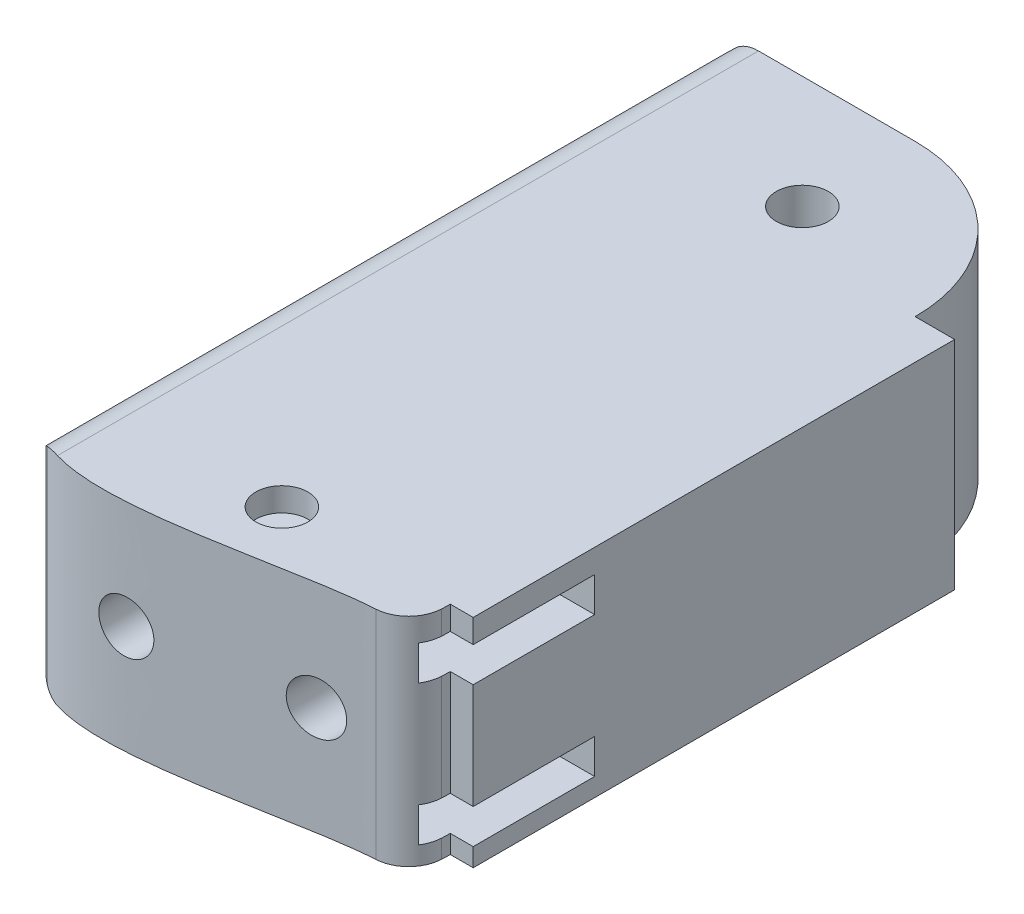
SolidWorks part; units mm, degrees
ref_plane "Front Plane" through (0, 0, 0) normal (0, 0, 1) x (1, 0, 0)
ref_plane "Top Plane" through (0, 0, 0) normal (0, 1, 0) x (1, 0, 0)
ref_plane "Right Plane" through (0, 0, 0) normal (1, 0, 0) x (0, 0, -1)
sketch "Sketch1" plane through (0, 0, 0) normal (0, 0, 1) x (1, 0, 0)
  line L0 (-24.2561, -24.0702) -> (-22.0061, -24.0702) construction
  line L1 (-24.2561, -17.8202) -> (-2.2017, -17.8202)
  line L2 (-24.2561, -17.8202) -> (-24.2561, -30.3202)
  line L3 (-24.2561, -30.3202) -> (-2.2017, -30.3202)
  line L4 (-2.2017, -17.8202) -> (-2.2017, -30.3202)
  line L5 (-2.2017, -24.0702) -> (-4.4517, -24.0702) construction
  line L6 (-22.0061, -24.0702) -> (-22.0061, -30.3202) construction
  line L7 (-4.4517, -24.0702) -> (-4.4517, -30.3202) construction
extrude "Boss-Extrude1" add sketch "Sketch1" along normal blind 43
sketch "Sketch2" plane through (0, -30.3202, 0) normal (0, -1, 0) x (1, 0, 0)
  line L0 (-3.524, 36.5) -> (-2.2017, 36.5)
  line L1 (-24.2561, 0) -> (-2.2017, 0) construction
  line L2 (-13.2289, 0) -> (-13.2289, 8.75) construction
  line L4 (-24.2561, 43) -> (-24.2561, 0) construction
  line L5 (-4.4789, 8.75) -> (-2.2017, 8.75)
  line L6 (-2.2017, 43) -> (-2.2017, 0) construction
  line L7 (-13.2289, 43) -> (-13.2289, 36.5) construction
  line L8 (-24.2561, 43) -> (-2.2017, 43) construction
  line L11 (-13.2289, 8.75) -> (-13.2289, 6.5) construction
  line L12 (-24.2561, 0) -> (-2.2017, 0) construction
  arc A1 (-13.2289, 0) -> (-4.4789, 8.75) centre (-13.2289, 8.75) ccw
  circle A4 centre (-13.2289, 6.5) radius 1.5
  arc A6 (-3.524, 36.5) -> (-3.8316, 38.9241) centre (-13.2289, 36.5) ccw
  circle A7 centre (-13.2289, 36.5) radius 1.5
  spline S0 degree 3 poles (-2.2017, 8.75) (5.3921, 3.8803) (-0.7771, -4.5233) (-17.1743, -10.6233) (-34.8214, -0.026) (-24.2561, 8.75) knots 0 0 0 0 0.283273 0.504245 1 1 1 1
  spline S1 degree 3 poles (-24.2561, 33.8451) (-30.4109, 43.5575) (-12.6056, 54.8557) (11.2773, 42.5746) (-2.2017, 36.5) knots 0 0 0 0 0.503105 1 1 1 1
  spline S2 degree 1 poles (-13.2289, 0) (-23.4906, 0) knots 0 0 1 1
  spline S3 degree 2 poles (-23.4906, 0) (-24.9665, 4.2378) (-24.2561, 8.75) knots 0 0 0 1 1 1
  spline S4 degree 3 poles (-3.8316, 38.9241) (-9.2507, 38.1251) (-28.5323, 46.1638) (-24.2561, 33.8451) knots 0 0 0 0 1 1 1 1
extrude "Cut-Extrude1" cut sketch "Sketch2" against normal blind 15 and the other way blind 10
fillet "Fillet3" radius 2 4 edges at (-24.2561, -17.8202, 21.0415) (-24.2561, -30.3202, 21.0415) (-24.2561, -24.0702, 3.0015) (-24.2561, -24.0702, 39.0815)
ref_plane "Plane1" through (0, 0, 0) normal (0, 0, 1) x (1, 0, 0)
sketch "Sketch5" plane through (0, 0, 0) normal (0, 0, 1) x (1, 0, 0)
  line L0 (-2.2017, -24.0702) -> (-8.4468, -24.0702) construction
  line L1 (-2.2017, -30.3202) -> (-24.2561, -30.3202) construction
  line L2 (-2.2017, -30.3202) -> (-2.2017, -17.8202) construction
  line L3 (-2.2017, -17.8202) -> (-24.2561, -17.8202) construction
  line L4 (-24.2561, -30.3202) -> (-24.2561, -17.8202) construction
  line L5 (-24.2561, -24.0702) -> (-18.0111, -24.0702) construction
  circle A0 centre (-18.0111, -24.0702) radius 1.5
  circle A1 centre (-8.4468, -24.0702) radius 1.5
extrude "Cut-Extrude4" cut sketch "Sketch5" along normal through all
ref_plane "Plane5" through (0, 0, 38) normal (0, 0, 1) x (1, 0, 0)
sketch "Sketch16" plane through (0, 0, 38) normal (0, 0, 1) x (1, 0, 0)
  line L0 (-2.2017, -17.681) -> (-2.2017, -19.181) construction
  line L1 (-2.2017, -17.681) -> (-24.2561, -17.681) construction
  line L2 (-2.2017, -17.681) -> (-2.2017, -30.7619) construction
  line L3 (-2.2017, -30.7619) -> (-24.2561, -30.7619) construction
  line L4 (-24.2561, -17.681) -> (-24.2561, -30.7619) construction
  line L5 (-2.2017, -17.681) -> (-24.2561, -30.7619) construction
  line L6 (-2.2017, -30.7619) -> (-24.2561, -17.681) construction
  line L7 (-2.2017, -30.7619) -> (-2.2017, -29.2619) construction
  line L9 (-2.2017, -19.181) -> (-24.2561, -19.181)
  line L10 (-2.2017, -19.181) -> (-2.2017, -21.181)
  line L11 (-2.2017, -21.181) -> (-24.2561, -21.181)
  line L12 (-24.2561, -19.181) -> (-24.2561, -21.181)
  line L13 (-2.2017, -19.181) -> (-24.2561, -21.181) construction
  line L14 (-2.2017, -21.181) -> (-24.2561, -19.181) construction
  line L15 (-2.2017, -29.2619) -> (-24.2561, -29.2619)
  line L16 (-2.2017, -29.2619) -> (-2.2017, -27.2619)
  line L17 (-2.2017, -27.2619) -> (-24.2561, -27.2619)
  line L18 (-24.2561, -29.2619) -> (-24.2561, -27.2619)
  line L19 (-2.2017, -29.2619) -> (-24.2561, -27.2619) construction
  line L20 (-2.2017, -27.2619) -> (-24.2561, -29.2619) construction
  point P4 (-13.2289, -24.2214)
  point P10 (-13.2289, -20.181)
  point P14 (-13.2289, -28.2619)
extrude "Cut-Extrude6" cut sketch "Sketch16" against normal blind 8.5
fillet "Fillet4" radius 2 1 edges at (-3.8316, -24.0702, 38.9241)
